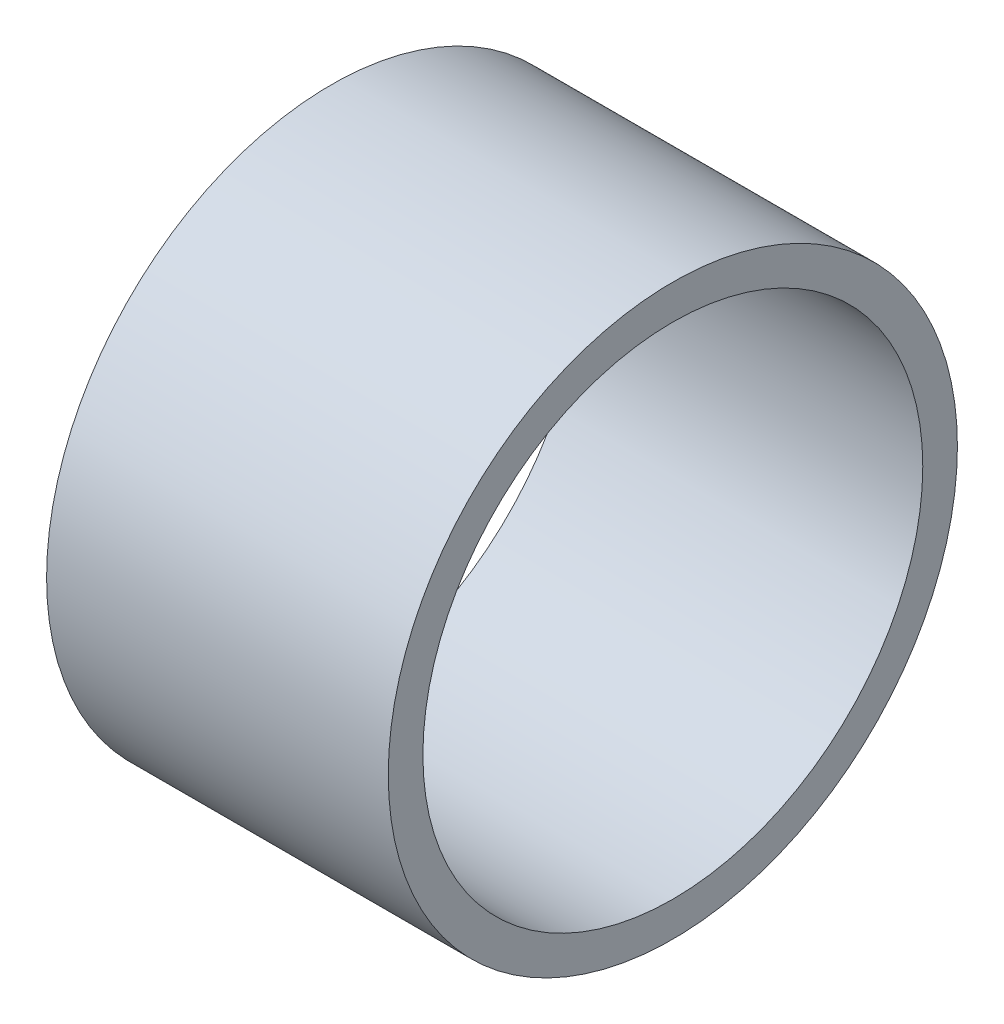
SolidWorks part; units mm, degrees
material "TPU 95A"
ref_plane "Front Plane" through (0, 0, 0) normal (1, 0, 0) x (0, 1, 0)
ref_plane "Top Plane" through (0, 0, 0) normal (0, 0, 1) x (0, 1, 0)
ref_plane "Right Plane" through (0, 0, 0) normal (0, 1, 0) x (-1, 0, 0)
sketch "Sketch1" plane through (0, 0, 0) normal (1, 0, 0) x (0, 1, 0)
  circle A0 centre (0, 0) radius 5.5
  circle A1 centre (0, 0) radius 6.262
  dimension "D1" = 11
  dimension "D2" = 12.524
extrude "Boss-Extrude1" add sketch "Sketch1" along normal blind 7.5184
equation "\"D1@Sketch1\"=11mm"
equation "\"D2@Sketch1\"=11mm+0.06"
